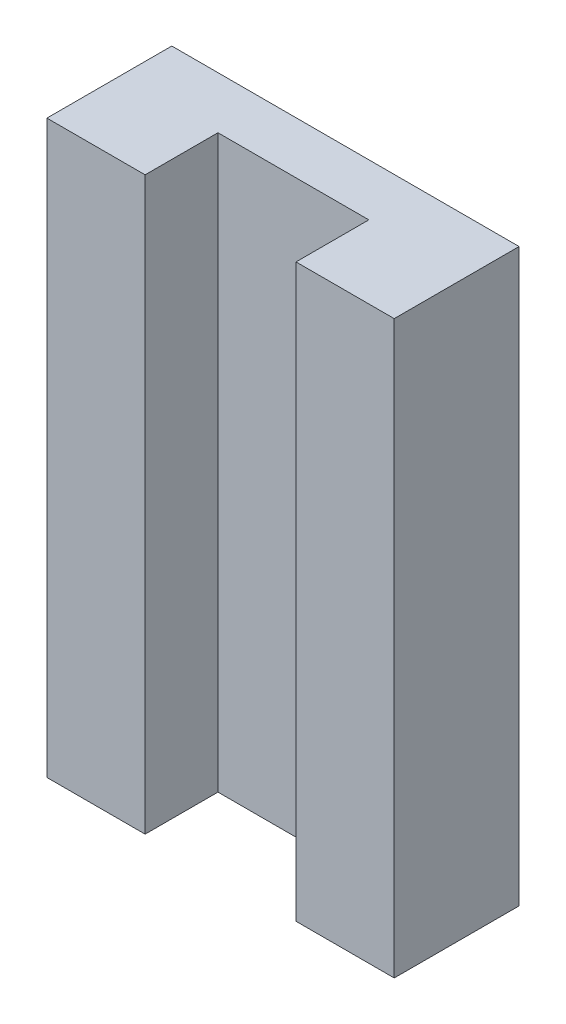
SolidWorks part; units mm, degrees
ref_plane "Front Plane" through (0, 0, 0) normal (0, 0, 1) x (1, 0, 0)
ref_plane "Top Plane" through (0, 0, 0) normal (0, 1, 0) x (1, 0, 0)
ref_plane "Right Plane" through (0, 0, 0) normal (1, 0, 0) x (0, 0, -1)
sketch "Sketch1" plane through (0, 0, 0) normal (0, 0, 1) x (1, 0, 0)
  line L1 (-13.35, 21.95) -> (13.35, 21.95)
  line L2 (-13.35, 21.95) -> (-13.35, -21.95)
  line L3 (-13.35, -21.95) -> (13.35, -21.95)
  line L4 (13.35, 21.95) -> (13.35, -21.95)
  line L5 (-13.35, 21.95) -> (13.35, -21.95) construction
  line L6 (-13.35, -21.95) -> (13.35, 21.95) construction
  point P0 (0, 0)
  dimension "D1" = 43.9
  dimension "D2" = 26.7
extrude "Boss-Extrude1" add sketch "Sketch1" along normal blind 9.6
sketch "Sketch2" plane through (0, 0, 9.6) normal (0, 0, 1) x (1, 0, 0)
  line L0 (13.35, 21.95) -> (-13.35, 21.95) construction
  line L1 (-5.8, 21.95) -> (5.8, 21.95)
  line L2 (-5.8, 21.95) -> (-5.8, -21.95)
  line L3 (-5.8, -21.95) -> (5.8, -21.95)
  line L4 (5.8, 21.95) -> (5.8, -21.95)
  line L5 (-13.35, -21.95) -> (13.35, -21.95) construction
  point P8 (0, -21.95)
  dimension "D1" = 11.6
extrude "Cut-Extrude1" cut sketch "Sketch2" against normal blind 5.6
sketch "Sketch3" plane through (0, 0, 0) normal (0, 0, -1) x (-1, 0, 0)
  line L0 (13.35, 21.95) -> (13.35, -21.95) construction
  line L1 (-13.35, 21.95) -> (13.35, 21.95) construction
  circle A0 centre (10.35, 10.15) radius 1.25
  circle A1 centre (10.35, -10.15) radius 1.25
  circle A2 centre (-10.35, -10.15) radius 1.25
  circle A3 centre (-10.35, 10.15) radius 1.25
  dimension "D1" = 2.5
  dimension "D2" = 3
  dimension "D3" = 11.8
extrude "Cut-Extrude2" cut sketch "Sketch3" against normal blind 4
thread "Thread1" pitch 0.5 method extrude profile "Thread Profile1" start angle 0, offset 0, length 0, pitch 0.5, diameter 2.5
ref_plane "Plane1" through (-9.1, 10.15, 0) normal (0, -1, 0) x (1, 0, 0)
sketch "Thread Profile1" plane through (-9.1, 10.15, 0) normal (0, -1, 0) x (1, 0, 0)
  line L0 (0, 0) -> (0, 0.5) construction
  line L11 (0, 0) -> (0, 0.4375)
  line L12 (0, 0.4375) -> (-0.2706, 0.2812)
  line L13 (-0.2706, 0.2812) -> (-0.2706, 0.1562)
  line L15 (-0.2706, 0.1562) -> (0, 0)
  line L17 (-0.2706, 0.2187) -> (0, 0.2187) construction
  point P2 (0, 0)
  dimension "Pitch" = 0.5
  dimension "Profile_Angle" = 60
  dimension "Profile_Land" = 0.125
  dimension "Profile_Height" = 0.2706
mirror "Mirror1" about plane through (0, 0, 0) normal (1, 0, 0) of "Thread1"
mirror "Mirror2" about plane through (0, 0, 0) normal (0, 1, 0) of "Mirror1"
